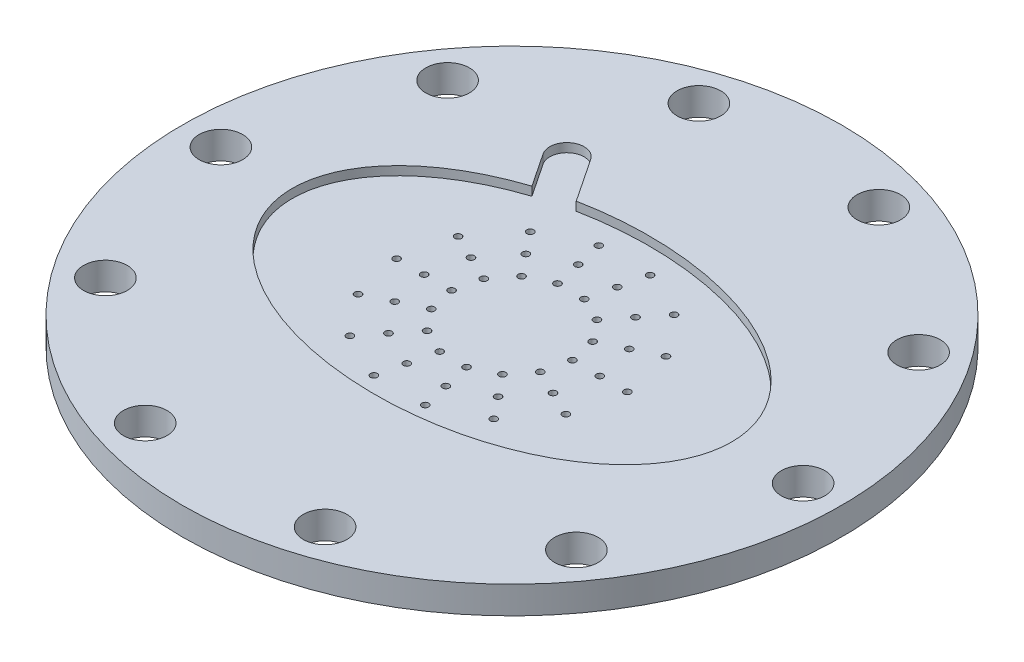
SolidWorks part; units mm, degrees
ref_plane "Front Plane" through (0, 0, 0) normal (0, 0, 1) x (1, 0, 0)
ref_plane "Top Plane" through (0, 0, 0) normal (0, 1, 0) x (1, 0, 0)
ref_plane "Right Plane" through (0, 0, 0) normal (1, 0, 0) x (0, 0, -1)
sketch "Sketch1" plane through (0, 0, 0) normal (0, 0, 1) x (1, 0, 0)
  line L0 (0, -6.35) -> (54.8259, -6.35)
  line L1 (0, 0) -> (76.2, 0)
  line L2 (0, 0) -> (0, -6.35)
  line L4 (76.2, 0) -> (76.2, -6.35)
  line L5 (54.8259, -6.35) -> (54.8259, -3.6576)
  line L6 (54.8259, -3.6576) -> (58.8899, -3.6576)
  line L7 (58.8899, -3.6576) -> (58.8899, -6.35)
  line L8 (58.8899, -6.35) -> (76.2, -6.35)
  dimension "D1" = 6.35
  dimension "D2" = 76.2
  dimension "D3" = 58.8899
  dimension "D4" = 4.064
  dimension "D5" = 2.6924
revolve "Revolve1" add sketch "Sketch1" angle 360 about L2
sketch "Sketch2" plane through (0, 0, 0) normal (0, 1, 0) x (1, 0, 0)
  line L0 (0, 0) -> (67.31, 0) construction
  dimension "D1" = 67.31
ref_axis "Axis1" through (0, 0.3175, 0) along (0, -1, 0)
hole_wizard "3/8 Clearance Hole1" positions "3DSketch2" profile "Sketch4" hole size "3/8" standard "ANSI Inch" end condition through all
sketch3d "3DSketch2"
  point P0 (67.31, 0, 0)
sketch "Sketch4" plane through (67.31, 0, 0) normal (1, 0, 0) x (0, 0, 1)
  line L0 (0, 0) -> (0, 6.35)
  line L1 (0, 6.35) -> (5.0419, 6.35)
  line L2 (5.0419, 6.35) -> (5.0419, 0)
  line L5 (5.0419, 0) -> (0, 0)
  line L11 (0, -6.35) -> (0, 107.95) construction
  dimension "Thru Hole Dia." = 10.0838
  dimension "Thru Hole Depth" = 6.35
pattern_circular "CirPattern1" count 10 over 360 about axis through (0, 0.3175, 0) along (0, -1, 0) of "3/8 Clearance Hole1"
sketch "Sketch5" plane through (0, 0, 0) normal (0, 1, 0) x (1, 0, 0)
  line L0 (-50.8, 0) -> (50.8, 0) construction
  line L1 (0, 0) -> (-25.4, 38.1) construction
  line L2 (-3.3022, -2.2015) -> (-28.7022, 35.8985)
  line L3 (3.3022, 2.2015) -> (-22.0978, 40.3015)
  arc A0 (-3.3022, -2.2015) -> (3.3022, 2.2015) centre (0, 0) ccw
  arc A1 (-22.0978, 40.3015) -> (-28.7022, 35.8985) centre (-25.4, 38.1) ccw
  ellipse E0 centre (0, 0) end of major axis (50.8, 0) minor radius 31.75
  point P10 (-12.7, 19.05)
  dimension "D5" = 3.9688
  dimension "D1" = 31.75
  dimension "D2" = 50.8
  dimension "D3" = 25.4
  dimension "D4" = 38.1
extrude "Cut-Extrude1" cut sketch "Sketch5" against normal blind 2.032 contours E0 | L3 A1 L2 A0
sketch "Sketch6" plane through (0, -2.032, 0) normal (0, 1, 0) x (1, 0, 0)
  line L0 (0, 0) -> (50.8, 0) construction
  circle A0 centre (13.97, 0) radius 0.7937
  circle A1 centre (20.32, 0) radius 0.7937
  circle A2 centre (26.67, 0) radius 0.7937
  circle A3 centre (12.5865, -6.0614) radius 0.7937
  circle A4 centre (18.3077, -8.8165) radius 0.7937
  circle A5 centre (24.0288, -11.5717) radius 0.7937
  circle A6 centre (8.7102, -10.9222) radius 0.7937
  circle A7 centre (12.6693, -15.8868) radius 0.7937
  circle A8 centre (16.6285, -20.8514) radius 0.7937
  circle A9 centre (3.1086, -13.6197) radius 0.7938
  circle A10 centre (4.5216, -19.8105) radius 0.7938
  circle A11 centre (5.9346, -26.0013) radius 0.7938
  circle A12 centre (-3.1086, -13.6197) radius 0.7937
  circle A13 centre (-4.5216, -19.8105) radius 0.7938
  circle A14 centre (-5.9346, -26.0013) radius 0.7938
  circle A15 centre (-8.7102, -10.9222) radius 0.7937
  circle A16 centre (-12.6693, -15.8868) radius 0.7937
  circle A17 centre (-16.6285, -20.8514) radius 0.7937
  circle A18 centre (-12.5865, -6.0614) radius 0.7937
  circle A19 centre (-18.3077, -8.8165) radius 0.7937
  circle A20 centre (-24.0288, -11.5717) radius 0.7937
  circle A21 centre (-13.97, 0) radius 0.7937
  circle A22 centre (-20.32, 0) radius 0.7937
  circle A23 centre (-26.67, 0) radius 0.7937
  circle A24 centre (-12.5865, 6.0614) radius 0.7937
  circle A25 centre (-18.3077, 8.8165) radius 0.7937
  circle A26 centre (-24.0288, 11.5717) radius 0.7937
  circle A27 centre (-8.7102, 10.9222) radius 0.7937
  circle A28 centre (-12.6693, 15.8868) radius 0.7937
  circle A29 centre (-16.6285, 20.8514) radius 0.7937
  circle A30 centre (-3.1086, 13.6197) radius 0.7938
  circle A31 centre (-4.5216, 19.8105) radius 0.7938
  circle A32 centre (-5.9346, 26.0013) radius 0.7938
  circle A33 centre (3.1086, 13.6197) radius 0.7937
  circle A34 centre (4.5216, 19.8105) radius 0.7938
  circle A35 centre (5.9346, 26.0013) radius 0.7938
  circle A36 centre (8.7102, 10.9222) radius 0.7937
  circle A37 centre (12.6693, 15.8868) radius 0.7937
  circle A38 centre (16.6285, 20.8514) radius 0.7937
  circle A39 centre (12.5865, 6.0614) radius 0.7937
  circle A40 centre (18.3077, 8.8165) radius 0.7937
  circle A41 centre (24.0288, 11.5717) radius 0.7937
  ellipse E0 centre (0, 0) end of major axis (50.8, 0) minor radius 31.75 (-23.5292, 28.139) -> (-15.4007, 30.2558) ccw construction
  ellipse E1 centre (0, 0) end of major axis (50.8, 0) minor radius 31.75 (-23.5292, 28.139) -> (-15.4007, 30.2558) ccw construction
  point P104 (0, 0)
  dimension "D1" = 1.5875
  dimension "D5" = 1.5875
  dimension "D6" = 1.5875
  dimension "D2" = 13.97
  dimension "D3" = 6.35
  dimension "D4" = 6.35
  dimension "D7" = 14
extrude "Cut-Extrude2" cut sketch "Sketch6" against normal through all
